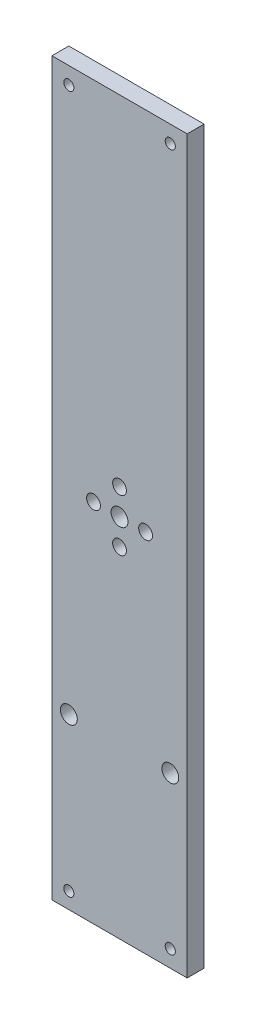
SolidWorks part; units mm, degrees
ref_plane "Front Plane" through (0, 0, 0) normal (0, 0, 1) x (1, 0, 0)
ref_plane "Top Plane" through (0, 0, 0) normal (0, 1, 0) x (1, 0, 0)
ref_plane "Right Plane" through (0, 0, 0) normal (1, 0, 0) x (0, 0, -1)
sketch "Sketch1" plane through (0, 0, 0) normal (0, 0, 1) x (1, 0, 0)
  line L1 (0, 0) -> (50.8, 0)
  line L2 (0, 0) -> (0, 274.6)
  line L3 (0, 274.6) -> (50.8, 274.6)
  line L4 (50.8, 0) -> (50.8, 274.6)
  dimension "D1" = 50.8
  dimension "D2" = 274.6
extrude "Extrude1" add sketch "Sketch1" along normal blind 6.35
hole_wizard "#10-24 Tapped Hole1" positions "3DSketch1" profile "Sketch2" tap size "#10-24" standard "Ansi Inch" end condition up to next
sketch3d "3DSketch1"
  line L0 (0, 0, 6.35) -> (50.8, 0, 6.35) construction
  line L1 (50.8, 274.6, 6.35) -> (0, 274.6, 6.35) construction
  line L2 (0, 274.6, 6.35) -> (0, 0, 6.35) construction
  point P0 (6.35, 6.096, 6.35)
  point P2 (44.4492, 6.35, 6.35)
  point P4 (44.45, 268.25, 6.35)
  point P6 (6.35, 268.25, 6.35)
  dimension "D1" = 6.096
  dimension "D2" = 6.35
  dimension "D3" = 6.35
  dimension "D4" = 6.35
  dimension "D5" = 38.1
  dimension "D6" = 38.1
  dimension "D7" = 6.35
  dimension "D8" = 6.35
sketch "Sketch2" plane through (6.35, 6.096, 6.35) normal (1, 0, 0) x (0, -1, 0)
  line L0 (0, 0) -> (0, 6.35)
  line L1 (0, 6.35) -> (1.8986, 6.35)
  line L2 (1.8986, 6.35) -> (1.8986, 0)
  line L5 (1.8986, 0) -> (0, 0)
  line L11 (0, -6.35) -> (0, 107.95) construction
  dimension "Thread Major Dia." = 3.7973
  dimension "Thru Tap Drill Depth" = 6.35
sketch "Sketch3" plane through (0, 0, 6.35) normal (0, 0, 1) x (1, 0, 0)
  line L0 (0, 0) -> (50.8, 274.6) construction
  circle A0 centre (25.4, 137.3) radius 3.175
  dimension "D1" = 6.35
extrude "Extrude2" cut sketch "Sketch3" against normal up to next
hole_wizard "#6 (0.204) Diameter Hole1" positions "3DSketch2" profile "Sketch4" hole size "#6" standard "Ansi Inch" end condition up to next
sketch3d "3DSketch2"
  line L0 (25.4, 137.3, 0) -> (25.4, 137.3, 6.35) construction
  line L1 (25.4, 127.521, 6.35) -> (25.4, 147.079, 6.35)
  line L3 (15.621, 137.3, 6.35) -> (35.179, 137.3, 6.35)
  circle A0 centre (25.4, 137.3, 6.35) radius 9.779
  point P0 (25.4, 147.079, 6.35)
  point P2 (25.4, 127.521, 6.35)
  point P4 (35.179, 137.3, 6.35)
  point P6 (15.621, 137.3, 6.35)
  point P11 (25.4, 137.3, 16.129)
  dimension "D1" = 19.558
sketch "Sketch4" plane through (25.4, 147.079, 6.35) normal (1, 0, 0) x (0, -1, 0)
  line L0 (0, 0) -> (0, 6.35)
  line L1 (0, 6.35) -> (2.5908, 6.35)
  line L2 (2.5908, 6.35) -> (2.5908, 0)
  line L5 (2.5908, 0) -> (0, 0)
  line L11 (0, -6.35) -> (0, 107.95) construction
  dimension "Thru Hole Dia." = 5.1816
  dimension "Thru Hole Depth" = 6.35
hole_wizard "1/4 (0.25) Diameter Hole1" positions "3DSketch3" profile "Sketch5" hole size "1/4" standard "Ansi Inch" end condition up to next
sketch3d "3DSketch3"
  line L0 (0, 274.6, 6.35) -> (0, 0, 6.35) construction
  line L1 (50.8, 0, 6.35) -> (50.8, 274.6, 6.35) construction
  line L3 (0, 0, 6.35) -> (50.8, 0, 6.35) construction
  point P0 (6.35, 63.5, 6.35)
  point P2 (44.45, 63.5, 6.35)
  dimension "D1" = 6.35
  dimension "D2" = 6.35
  dimension "D3" = 63.5
  dimension "D4" = 63.5
sketch "Sketch5" plane through (6.35, 63.5, 6.35) normal (1, 0, 0) x (0, -1, 0)
  line L0 (0, 0) -> (0, 6.35)
  line L1 (0, 6.35) -> (3.175, 6.35)
  line L2 (3.175, 6.35) -> (3.175, 0)
  line L5 (3.175, 0) -> (0, 0)
  line L11 (0, -6.35) -> (0, 107.95) construction
  dimension "Thru Hole Dia." = 6.35
  dimension "Thru Hole Depth" = 6.35
